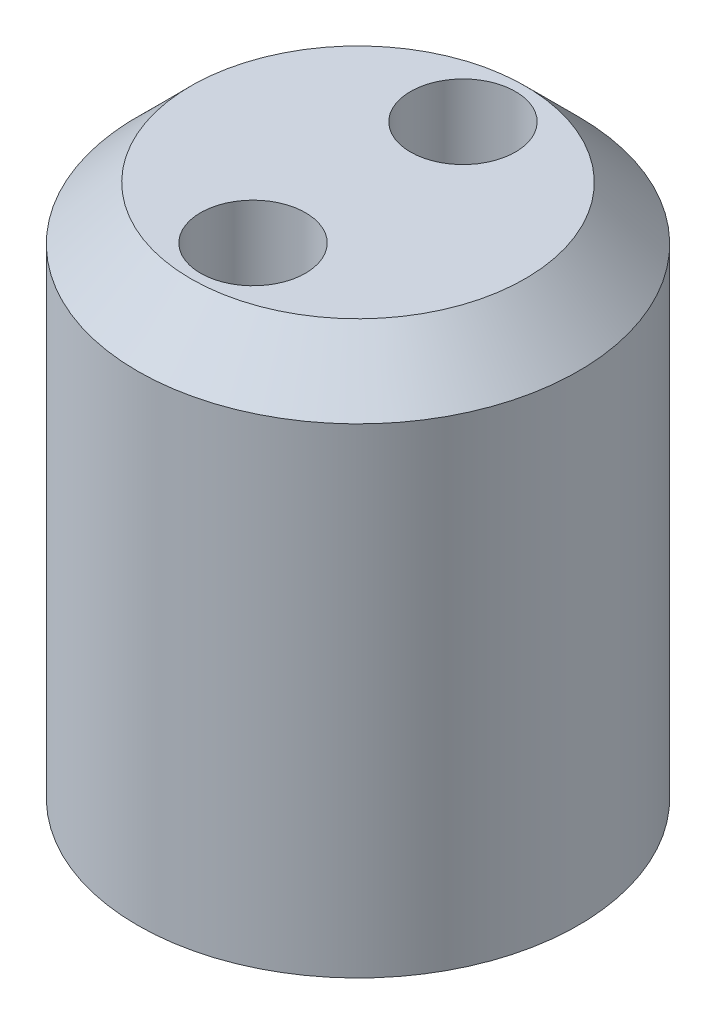
SolidWorks part; units mm, degrees
ref_plane "Front Plane" through (0, 0, 0) normal (0, 0, 1) x (1, 0, 0)
ref_plane "Top Plane" through (0, 0, 0) normal (0, 1, 0) x (1, 0, 0)
ref_plane "Right Plane" through (0, 0, 0) normal (1, 0, 0) x (0, 0, -1)
sketch "Sketch1" plane through (0, 0, 0) normal (0, 1, 0) x (1, 0, 0)
  line L0 (0, -5) -> (0, 5) construction
  circle A0 centre (0, 0) radius 10.5
  circle A2 centre (0, 5) radius 2.5
  circle A3 centre (0, -5) radius 2.5
  dimension "D1" = 21
  dimension "D2" = 5
  dimension "D3" = 10
extrude "Boss-Extrude1" add sketch "Sketch1" along normal blind 25.4
chamfer "Chamfer1" distance 2.54 angle 45 1 edges at (0, 25.4, 10.5)
equation "\"cf_tube_outer_diameter\"= 25mm"
equation "\"cf_tube_inner_diameter\" = 21mm"
equation "\"mid_plate_mid_to_top\" = 100mm"
equation "\"mid_plate_mid_to_bottom\" = 30mm"
equation "\"mid_plate_horizontal_spacing\"=250mm"
equation "\"cf_plate_thickness\" =3mm"
equation "\"mid_tube_length\" = 500mm"
equation "\"D1@Sketch1\"=\"cf_tube_inner_diameter\""
